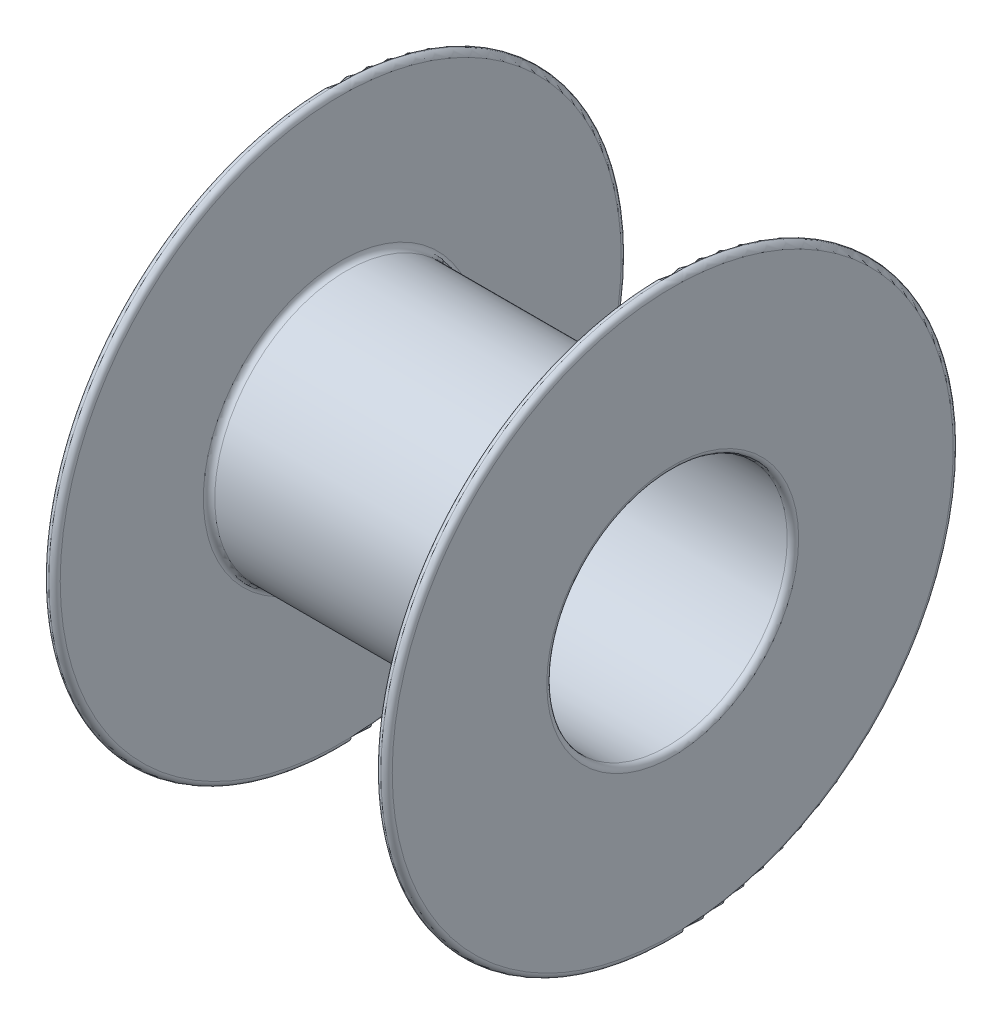
SolidWorks part; units mm, degrees
material "Acrylic (Medium-high impact)"
ref_plane "Front Plane" through (0, 0, 0) normal (0, 0, 1) x (1, 0, 0)
ref_plane "Top Plane" through (0, 0, 0) normal (0, 1, 0) x (1, 0, 0)
ref_plane "Right Plane" through (0, 0, 0) normal (1, 0, 0) x (0, 0, -1)
sketch "Sketch1" plane through (0, 0, 0) normal (1, 0, 0) x (0, 0, -1)
  circle A0 centre (0, 0) radius 10.5
  circle A1 centre (0, 0) radius 11.5
  circle A2 centre (0, 0) radius 25
  dimension "D2" = 21
  dimension "D3" = 50
  dimension "D1" = 1
extrude "Boss-Extrude1" add sketch "Sketch1" along normal mid plane 30 contours A1 A0 region at (0, 0, 11.1747)
extrude "Boss-Extrude2" add sketch "Sketch1<3>" along normal blind 1 from offset 14 contours A2 A1 region at (0, 0, 24.2929)
sketch "Sketch1<3>" plane through (0, 0, 0) normal (1, 0, 0) x (0, 0, -1) same geometry as "Sketch1"
extrude "Boss-Extrude3" add sketch "Sketch1<4>" against normal blind 1 from offset 14 contours A2 A1 region at (0, 0, 24.2929) offset against normal yes
sketch "Sketch1<4>" plane through (0, 0, 0) normal (1, 0, 0) x (0, 0, -1) same geometry as "Sketch1"
fillet "Fillet1" radius 0.5 8 edges at (-14, 0, -11.5) (-14, 0, -25) (-15, 0, -25) (14, 0, -25) (-15, 0, -10.5) (15, 0, -10.5) (14, 0, -11.5) (15, 0, -25)
